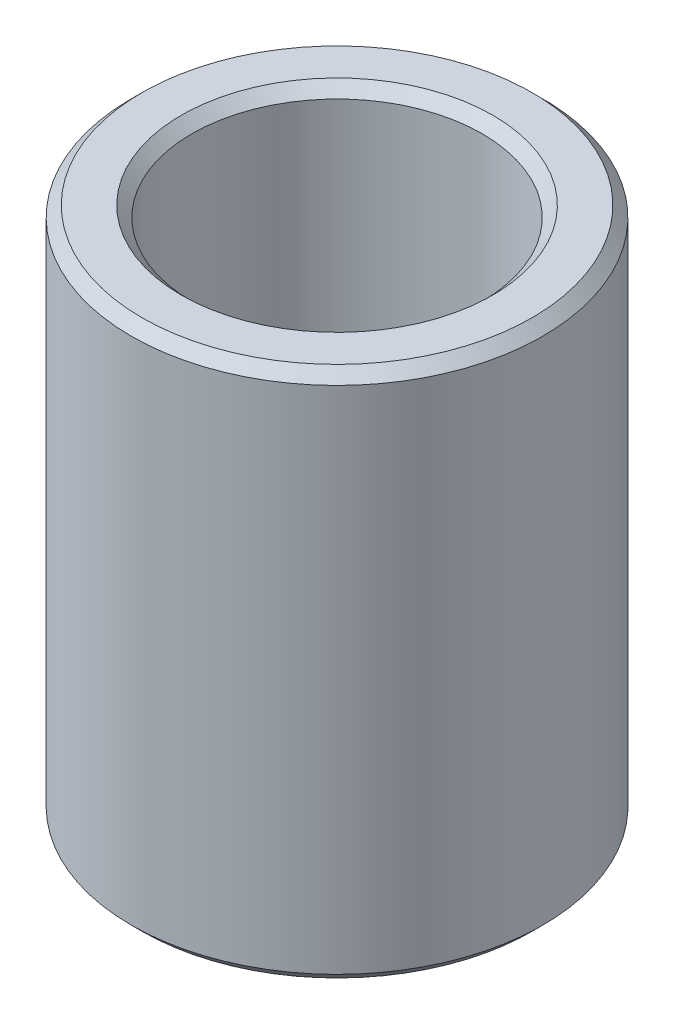
SolidWorks part; units mm, degrees
ref_plane "Front Plane" through (0, 0, 0) normal (0, 0, 1) x (1, 0, 0)
ref_plane "Top Plane" through (0, 0, 0) normal (0, 1, 0) x (1, 0, 0)
ref_plane "Right Plane" through (0, 0, 0) normal (1, 0, 0) x (0, 0, -1)
sketch "Sketch1" plane through (0, 0, 0) normal (0, 1, 0) x (1, 0, 0)
  circle A0 centre (0, 0) radius 45
  dimension "SLEEVE_OD" = 90
extrude "Boss-Extrude1" add sketch "Sketch1" along normal blind 116.2501
sketch "Sketch2" plane through (0, 0, 0) normal (0, 1, 0) x (1, 0, 0)
  circle A0 centre (0, 0) radius 31.7489
  dimension "BORE_D" = 63.4978
extrude "Cut-Extrude1" cut sketch "Sketch2" along normal through all
chamfer "Chamfer1" distance 2.3345 angle 45 4 edges at (0, 116.2501, 31.7489) (0, 0, 31.7489) (0, 0, 45) (0, 116.2501, 45)
